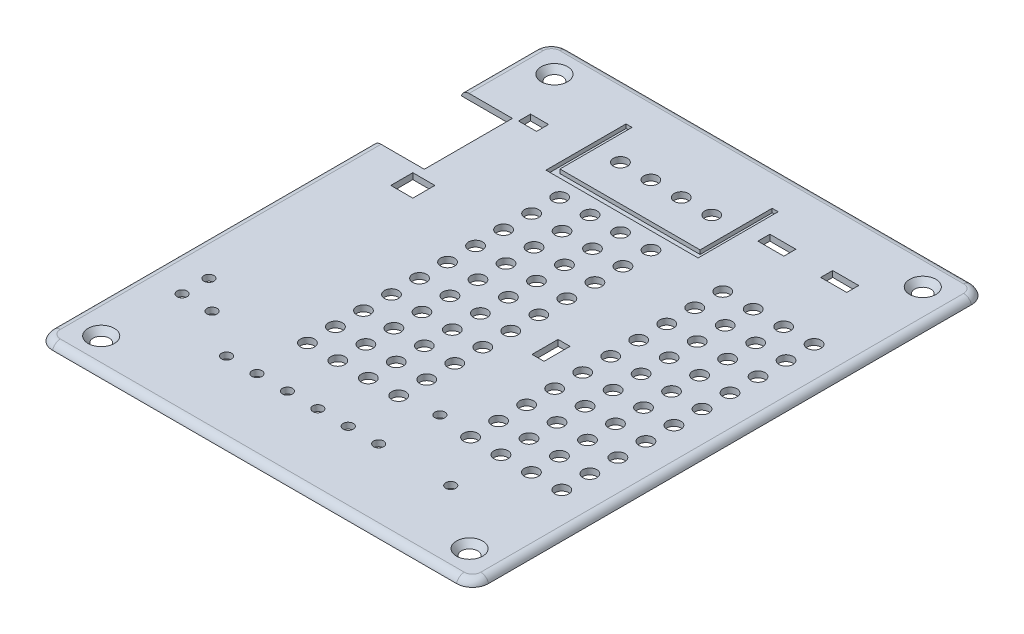
SolidWorks part; units mm, degrees
ref_plane "Přední rovina" through (0, 0, 0) normal (0, 0, 1) x (1, 0, 0)
ref_plane "Horní rovina" through (0, 0, 0) normal (0, 1, 0) x (1, 0, 0)
ref_plane "Pravá rovina" through (0, 0, 0) normal (1, 0, 0) x (0, 0, -1)
sketch "Skica1" plane through (0, 0, 0) normal (0, 1, 0) x (1, 0, 0)
  line L1 (-54.445, -64.3) -> (54.445, -64.3)
  line L2 (-54.445, -64.3) -> (-54.445, 64.3)
  line L3 (-54.445, 64.3) -> (54.445, 64.3)
  line L4 (54.445, -64.3) -> (54.445, 64.3)
  line L5 (-54.445, -64.3) -> (54.445, 64.3) construction
  line L6 (-54.445, 64.3) -> (54.445, -64.3) construction
  point P0 (0, 0)
  dimension "D1" = 108.89
  dimension "D2" = 128.6
extrude "Přidat vysunutím1" add sketch "Skica1" along normal blind 1.5
fillet "Zaoblit1" radius 4 4 edges at (54.445, 0.75, -64.3) (54.445, 0.75, 64.3) (-54.445, 0.75, -64.3) (-54.445, 0.75, 64.3)
fillet "Zaoblit2" radius 2 8 edges at (53.2734, 1.5, 63.1284) (0, 1.5, 64.3) (-53.2734, 1.5, 63.1284) (-54.445, 1.5, 0) (-53.2734, 1.5, -63.1284) (0, 1.5, -64.3) (53.2734, 1.5, -63.1284) (54.445, 1.5, 0)
sketch "Skica2" plane through (0, 0, 0) normal (0, -1, 0) x (1, 0, 0)
  line L0 (0, 68.8192) -> (0, -71.6902) construction
  line L1 (-80.8942, 0) -> (91.0271, 0) construction
  circle A0 centre (-46, 56.6) radius 1.6
  dimension "D1" = 3.2
  dimension "D2" = 46
  dimension "D3" = 56.6
extrude "Odebrat vysunutím1" cut sketch "Skica2" against normal blind 3
pattern_linear "LinPole1" count 2 spacing 113.2 along (0, 0, -1) count 2 spacing 92 along (1, 0, 0) of "Odebrat vysunutím1"
chamfer "Zkosení1" distance 2 angle 40 4 edges at (46, 1.5, 55) (46, 1.5, -58.2) (-46, 1.5, -58.2) (-46, 1.5, 55) first distance on face at (46, 0, 55) first distance on face at (46, 0, -58.2) first distance on face at (-46, 0, -58.2) first distance on face at (-46, 0, 55)
sketch "Skica3" plane through (0, 1.5, 0) normal (0, 1, 0) x (1, 0, 0)
  line L3 (-50, -50) -> (50, -50) construction
  line L4 (-50, -50) -> (-50, 50) construction
  line L5 (-50, 50) -> (50, 50) construction
  line L6 (50, -50) -> (50, 50) construction
  line L7 (-50, -50) -> (50, 50) construction
  line L8 (-50, 50) -> (50, -50) construction
  circle A0 centre (44.83, -32.38) radius 1.75
  circle A1 centre (4.08, -32.38) radius 1.75
  circle A2 centre (4.08, 45.8) radius 1.75
  point P7 (0, 0)
  dimension "D2" = 3.5
  dimension "D6" = 3.5
  dimension "D11" = 3.5
  dimension "D1" = 5.17
  dimension "D3" = 17.62
  dimension "D4" = 100
  dimension "D5" = 100
  dimension "D7" = 45.92
  dimension "D8" = 17.62
  dimension "D9" = 45.92
  dimension "D10" = 4.2
extrude "Odebrat vysunutím3" cut sketch "Skica3" against normal blind 4 contours A0 region at (44.83, 1.5, 32.38)
pattern_linear "LinPole3" count 10 spacing 7 along (0, 0, -1) count 4 spacing 7.6 along (-1, 0, 0) of "Odebrat vysunutím3"
extrude "Odebrat vysunutím4" cut sketch "Skica3<3>" against normal blind 4 contours A1 region at (4.08, 1.5, 32.38)
sketch "Skica3<3>" plane through (0, 1.5, 0) normal (0, 1, 0) x (1, 0, 0) same geometry as "Skica3"
pattern_linear "LinPole4" count 10 spacing 7 along (0, 0, -1) count 4 spacing 7.6 along (-1, 0, 0) of "Odebrat vysunutím4"
extrude "Odebrat vysunutím5" cut sketch "Skica3<4>" against normal blind 10
sketch "Skica3<4>" plane through (0, 1.5, 0) normal (0, 1, 0) x (1, 0, 0) same geometry as "Skica3"
pattern_linear "LinPole5" count 4 spacing 7.6 along (-1, 0, 0) of "Odebrat vysunutím5"
sketch "Skica4" plane through (0, 1.5, 0) normal (0, 1, 0) x (1, 0, 0)
  line L1 (-50, -50) -> (50, -50) construction
  line L2 (-50, -50) -> (-50, 50) construction
  line L3 (-50, 50) -> (50, 50) construction
  line L4 (50, -50) -> (50, 50) construction
  line L5 (-50, -50) -> (50, 50) construction
  line L6 (-50, 50) -> (50, -50) construction
  line L7 (15.5, 48.9) -> (22, 48.9)
  line L8 (15.5, 48.9) -> (15.5, 45.9)
  line L9 (15.5, 45.9) -> (22, 45.9)
  line L10 (22, 48.9) -> (22, 45.9)
  line L11 (15.5, 48.9) -> (22, 45.9) construction
  line L12 (15.5, 45.9) -> (22, 48.9) construction
  line L13 (31.2, 48.9) -> (37.7, 48.9)
  line L14 (31.2, 48.9) -> (31.2, 45.9)
  line L15 (31.2, 45.9) -> (37.7, 45.9)
  line L16 (37.7, 48.9) -> (37.7, 45.9)
  line L17 (31.2, 48.9) -> (37.7, 45.9) construction
  line L18 (31.2, 45.9) -> (37.7, 48.9) construction
  line L19 (11.8, -0.3) -> (14.8, -0.3)
  line L20 (11.8, -0.3) -> (11.8, -6.8)
  line L21 (11.8, -6.8) -> (14.8, -6.8)
  line L22 (14.8, -0.3) -> (14.8, -6.8)
  line L23 (11.8, -0.3) -> (14.8, -6.8) construction
  line L24 (11.8, -6.8) -> (14.8, -0.3) construction
  circle A0 centre (13.38, -31.4) radius 1.25
  circle A2 centre (30, -45.3) radius 1.25
  circle A3 centre (-45, -37.4) radius 1.25
  circle A4 centre (-45, -30.7) radius 1.25
  circle A5 centre (-37.52, -37.4) radius 1.25
  point P0 (0, 0)
  point P6 (18.75, 47.4)
  point P11 (34.45, 47.4)
  point P16 (13.3, -3.55)
  point P21 (13.3, -0.3)
  dimension "D13" = 2.5
  dimension "D16" = 12.48
  dimension "D17" = 2.5
  dimension "D23" = 2.5
  dimension "D24" = 2.5
  dimension "D25" = 2.5
  dimension "D1" = 100
  dimension "D2" = 100
  dimension "D3" = 3
  dimension "D4" = 6.5
  dimension "D5" = 1.1
  dimension "D6" = 1.1
  dimension "D7" = 12.3
  dimension "D8" = 28
  dimension "D9" = 35.2
  dimension "D10" = 50.3
  dimension "D11" = 36.62
  dimension "D12" = 18.6
  dimension "D14" = 5
  dimension "D15" = 5
  dimension "D18" = 20
  dimension "4,5" = 4.7
  dimension "D20" = 80.7
  dimension "D21" = 87.4
  dimension "D22" = 87.4
extrude "Odebrat vysunutím6" cut sketch "Skica4" against normal blind 10
sketch "Skica5" plane through (0, 1.5, 0) normal (0, 1, 0) x (1, 0, 0)
  line L1 (-50, 50) -> (50, 50) construction
  line L2 (-50, 50) -> (-50, -50) construction
  line L3 (-50, -50) -> (50, -50) construction
  line L4 (50, 50) -> (50, -50) construction
  line L5 (-50, 50) -> (50, -50) construction
  line L6 (-50, -50) -> (50, 50) construction
  circle A0 centre (-26, -45.3) radius 1.25
  point P0 (0, 0)
  dimension "D5" = 2.5
  dimension "D1" = 100
  dimension "D2" = 100
  dimension "D3" = 4.7
  dimension "D4" = 76
extrude "Odebrat vysunutím7" cut sketch "Skica5" against normal blind 10
pattern_linear "LinPole6" count 6 spacing 7.6 along (1, 0, 0) of "Odebrat vysunutím7"
sketch "Skica6" plane through (0, 1.5, 0) normal (0, 1, 0) x (1, 0, 0)
  line L1 (-42.39, 17.62) -> (-36.89, 17.62)
  line L2 (-42.39, 17.62) -> (-42.39, 12.12)
  line L3 (-42.39, 12.12) -> (-36.89, 12.12)
  line L4 (-36.89, 17.62) -> (-36.89, 12.12)
  line L5 (-42.39, 17.62) -> (-36.89, 12.12) construction
  line L6 (-42.39, 12.12) -> (-36.89, 17.62) construction
  line L7 (-41.7, 41.8) -> (-63.2133, 41.8)
  line L8 (-41.7, 41.8) -> (-41.7, 19.8)
  line L9 (-41.7, 19.8) -> (-63.2133, 19.8)
  line L10 (-63.2133, 41.8) -> (-63.2133, 19.8)
  line L11 (-41.7, 41.8) -> (-63.2133, 19.8) construction
  line L12 (-41.7, 19.8) -> (-63.2133, 41.8) construction
  line L14 (-50, 50) -> (50, 50) construction
  line L15 (-50, 50) -> (-50, -50) construction
  line L16 (-50, -50) -> (50, -50) construction
  line L17 (50, 50) -> (50, -50) construction
  line L18 (-50, 50) -> (50, -50) construction
  line L19 (-50, -50) -> (50, 50) construction
  line L20 (-40.37, 45) -> (-35.87, 45)
  line L21 (-40.37, 45) -> (-40.37, 42)
  line L22 (-40.37, 42) -> (-35.87, 42)
  line L23 (-35.87, 45) -> (-35.87, 42)
  line L24 (-40.37, 45) -> (-35.87, 42) construction
  line L25 (-40.37, 42) -> (-35.87, 45) construction
  point P0 (-39.64, 14.87)
  point P5 (-52.4567, 30.8)
  point P12 (0, 0)
  point P18 (-52.4567, 41.8)
  point P20 (-38.12, 43.5)
  dimension "D1" = 100
  dimension "D2" = 100
  dimension "D3" = 10.36
  dimension "D4" = 35.13
  dimension "D5" = 5.5
  dimension "D6" = 8.2
  dimension "D7" = 30.2
  dimension "D8" = 8.3
  dimension "D9" = 6.5
  dimension "D10" = 11.88
  dimension "D11" = 4.5
  dimension "D12" = 3
extrude "Odebrat vysunutím8" cut sketch "Skica6" against normal blind 10 contours L4 L1 L2 L3 | L23 L20 L21 L22 | L7 L10 L9 L8 region at (-39.64, 1.5, -14.87) region at (-38.12, 1.5, -43.5)
sketch "Skica7" plane through (0, 1.5, 0) normal (0, 1, 0) x (1, 0, 0)
  line L1 (-24.82, 36.8) -> (10.18, 36.8)
  line L2 (-24.82, 36.8) -> (-24.82, 34.8)
  line L3 (-24.82, 34.8) -> (10.18, 34.8)
  line L4 (10.18, 36.8) -> (10.18, 34.8)
  line L5 (-26.32, 54.8) -> (-24.82, 54.8)
  line L6 (-26.32, 54.8) -> (-26.32, 34.8)
  line L7 (-26.32, 34.8) -> (-24.82, 34.8)
  line L8 (-24.82, 54.8) -> (-24.82, 34.8)
  line L9 (11.68, 54.8) -> (10.18, 54.8)
  line L10 (11.68, 54.8) -> (11.68, 34.8)
  line L11 (11.68, 34.8) -> (10.18, 34.8)
  line L12 (10.18, 54.8) -> (10.18, 34.8)
  circle A0 centre (-11.12, 45.8) radius 1.75 construction
  circle A1 centre (-18.72, 45.8) radius 1.75 construction
  dimension "D2" = 9
  dimension "D6" = 2
  dimension "D1" = 35
  dimension "D3" = 20
  dimension "D4" = 1.5
  dimension "D5" = 6.1
extrude "Odebrat vysunutím9" cut sketch "Skica7" against normal blind 1 contours L4 L1 L2 L3 | L8 L5 L6 L7 L2 | L9 L12 L4 L11 L10 region at (-7.32, 1.5, -35.8) region at (-25.57, 1.5, -44.8) region at (10.93, 1.5, -44.8)
